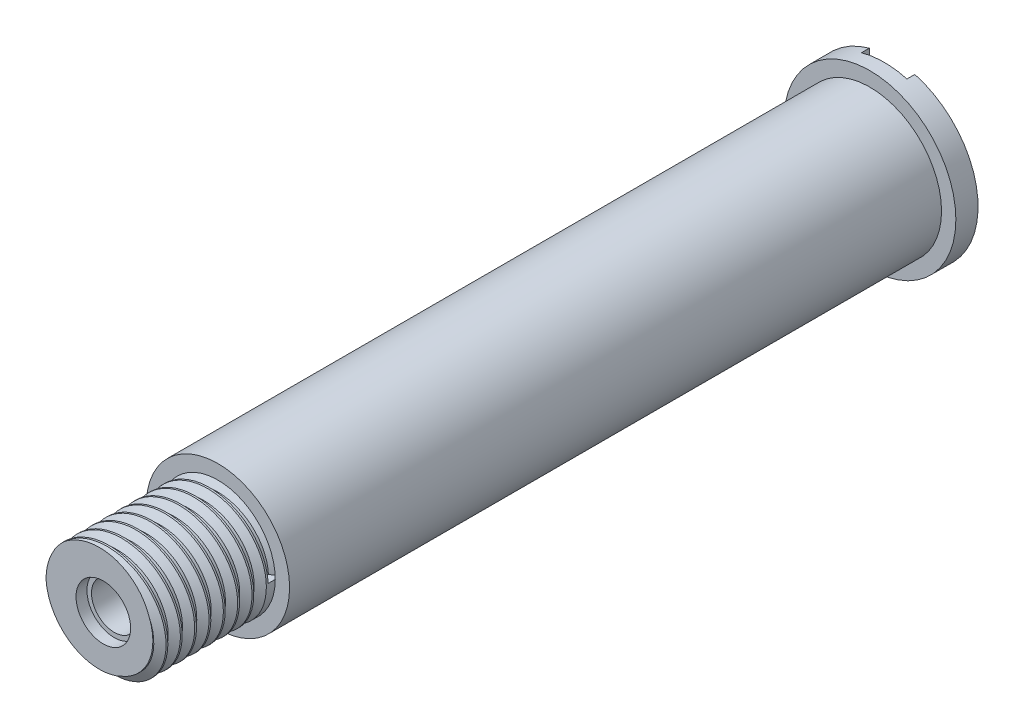
SolidWorks part; units mm, degrees
ref_plane "Front Plane" through (0, 0, 0) normal (0, 0, 1) x (1, 0, 0)
ref_plane "Top Plane" through (0, 0, 0) normal (0, 1, 0) x (1, 0, 0)
ref_plane "Right Plane" through (0, 0, 0) normal (1, 0, 0) x (0, 0, -1)
sketch "Sketch2" plane through (0, 0, 0) normal (0, 0, 1) x (1, 0, 0)
  circle A0 centre (0, 0) radius 6
extrude "Boss-Extrude1" add sketch "Sketch2" along normal blind 55.05
sketch "Sketch3" plane through (0, 0, 55.05) normal (0, 0, 1) x (1, 0, 0)
  circle A0 centre (0, 0) radius 5
  circle A1 centre (0, 0) radius 6
extrude "Cut-Extrude1" cut sketch "Sketch3" against normal blind 53.5 and the other way blind 1 contours A0 | A1
sketch "Sketch4" plane through (0, 0, 0) normal (0, 0, -1) x (-1, 0, 0)
  circle A0 centre (0, 0) radius 3.175
extrude "Cut-Extrude2" cut sketch "Sketch4" against normal blind 46
sketch "Sketch6" plane through (0, 0, 55.05) normal (0, 0, 1) x (1, 0, 0)
  circle A0 centre (0, 0) radius 1.5875
extrude "Cut-Extrude3" cut sketch "Sketch6" against normal blind 75.718
sketch "Sketch7" plane through (0, 0, 55.05) normal (0, 0, 1) x (1, 0, 0)
  circle A0 centre (0, 0) radius 1.905
extrude "Cut-Extrude4" cut sketch "Sketch7" against normal blind 0.762
sketch "Sketch8" plane through (0, 0, 0) normal (0, 0, -1) x (-1, 0, 0)
  line L0 (0, 0) -> (1.5875, 0)
  line L1 (1.5875, 0) -> (1.5875, 10.4234)
  line L2 (0, 0) -> (-1.5875, 0)
  line L3 (-1.5875, 0) -> (-1.5875, 10.4234)
  line L5 (-1.5875, 10.4234) -> (1.5875, 10.4234)
extrude "Cut-Extrude5" cut sketch "Sketch8" against normal blind 0.55
sketch "Sketch9" plane through (0, 0, 55.05) normal (0, 0, 1) x (1, 0, 0)
  circle A0 centre (0, 0) radius 4
  circle A1 centre (0, 0) radius 5
extrude "Cut-Extrude6" cut sketch "Sketch9" against normal blind 8
thread "Thread1" pitch 1 method cut profile "Thread Profile1" start angle 0, offset 1, length 8.5, pitch 1, diameter 8
ref_plane "Plane1" through (-4, 0, 56.05) normal (0, -1, 0) x (-1, 0, 0)
sketch "Thread Profile1" plane through (-4, 0, 56.05) normal (0, -1, 0) x (-1, 0, 0)
  line L0 (0, 0) -> (0, 1) construction
  line L11 (0, 0) -> (0, 0.875)
  line L12 (0, 0.875) -> (-0.5413, 0.5625)
  line L13 (-0.5413, 0.5625) -> (-0.5413, 0.3125)
  line L15 (-0.5413, 0.3125) -> (0, 0)
  line L17 (-0.5413, 0.4375) -> (0, 0.4375) construction
  point P2 (0, 0)
  dimension "Pitch" = 1
  dimension "Profile_Angle" = 60
  dimension "Profile_Land" = 0.25
  dimension "Profile_Height" = 0.5413
